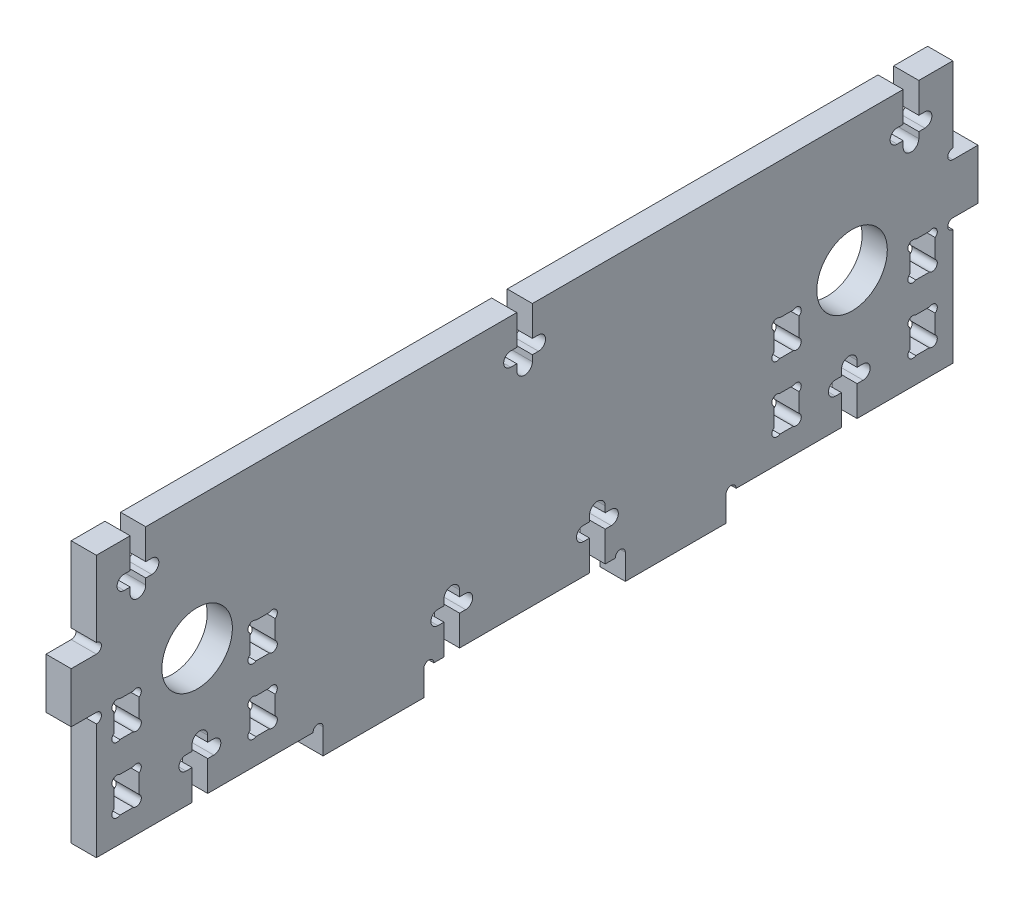
SolidWorks part; units mm, degrees
ref_plane "정면" through (0, 0, 0) normal (0, 0, 1) x (1, 0, 0)
ref_plane "윗면" through (0, 0, 0) normal (0, 1, 0) x (1, 0, 0)
ref_plane "우측면" through (0, 0, 0) normal (1, 0, 0) x (0, 0, -1)
sketch "스케치1" plane through (0, 0, 0) normal (1, 0, 0) x (0, 0, -1)
  line L1 (0, 0) -> (170, 0)
  line L2 (0, 0) -> (0, 52)
  line L3 (0, 52) -> (170, 52)
  line L4 (170, 0) -> (170, 52)
  dimension "D1" = 170
  dimension "D2" = 52
extrude "보스-돌출1" add sketch "스케치1" along normal blind 5
sketch "스케치2" plane through (5, 0, 0) normal (1, 0, 0) x (0, 0, -1)
  line L0 (170, 26) -> (150, 26) construction
  line L1 (170, 0) -> (170, 52) construction
  line L2 (150, 26) -> (20, 26) construction
  line L3 (20, 26) -> (0, 26) construction
  line L4 (0, 52) -> (0, 0) construction
  circle A0 centre (150, 26) radius 7
  circle A1 centre (20, 26) radius 7
  dimension "D2" = 14
  dimension "D1" = 20
extrude "컷-돌출1" cut sketch "스케치2" against normal blind 10
sketch "스케치3" plane through (5, 0, 0) normal (1, 0, 0) x (0, 0, -1)
  line L0 (0, 0) -> (170, 0) construction
  line L1 (45, 0) -> (65, 0)
  line L2 (45, 0) -> (45, -5)
  line L3 (45, -5) -> (65, -5)
  line L4 (65, 0) -> (65, -5)
  line L5 (0, -5) -> (45, -5) construction
  line L6 (65, -5) -> (105, -5) construction
  line L7 (125, 0) -> (105, 0)
  line L8 (125, 0) -> (125, -5)
  line L9 (125, -5) -> (105, -5)
  line L10 (105, 0) -> (105, -5)
  line L11 (125, -5) -> (170, -5) construction
  line L12 (170, -5) -> (170, 0) construction
  line L13 (0, 0) -> (0, -5) construction
  line L14 (0, 0) -> (0, -5) construction
  line L15 (0, -5) -> (45, -5) construction
  dimension "D1" = 45
  dimension "D2" = 20
extrude "보스-돌출2" add sketch "스케치3" against normal blind 5
sketch "스케치6" plane through (5, 0, 0) normal (1, 0, 0) x (0, 0, -1)
  line L0 (151, 0) -> (151, 6)
  line L1 (147.9, 10) -> (151, 10) construction
  line L2 (146.7, 6) -> (146.7, 8.8) construction
  line L3 (151, 6) -> (151, 8.8) construction
  line L4 (147.9, 0) -> (151, 0)
  line L5 (146.7, 8.8) -> (147.9, 8.8)
  line L6 (147.9, 0) -> (147.9, 6)
  line L7 (152.2, 8.8) -> (152.2, 6) construction
  line L8 (147.9, 6) -> (146.7, 6)
  line L9 (147.9, 8.8) -> (147.9, 6) construction
  line L10 (151, 8.8) -> (151, 10)
  line L11 (147.9, 6) -> (151, 6) construction
  line L12 (147.9, 8.8) -> (151, 8.8) construction
  line L13 (151, 8.8) -> (152.2, 8.8)
  line L14 (147.9, 8.8) -> (147.9, 10)
  line L15 (149.45, 10) -> (149.45, 12.1831) construction
  line L16 (152.2, 6) -> (151, 6)
  line L18 (65, 0) -> (105, 0) construction
  line L19 (101, 0) -> (101, 6)
  line L20 (97.9, 10) -> (101, 10) construction
  line L21 (96.7, 6) -> (96.7, 8.8) construction
  line L22 (101, 6) -> (101, 8.8) construction
  line L23 (97.9, 0) -> (101, 0)
  line L24 (96.7, 8.8) -> (97.9, 8.8)
  line L25 (97.9, 0) -> (97.9, 6)
  line L26 (102.2, 8.8) -> (102.2, 6) construction
  line L27 (97.9, 6) -> (96.7, 6)
  line L28 (97.9, 8.8) -> (97.9, 6) construction
  line L29 (101, 8.8) -> (101, 10)
  line L30 (97.9, 6) -> (101, 6) construction
  line L31 (97.9, 8.8) -> (101, 8.8) construction
  line L32 (101, 8.8) -> (102.2, 8.8)
  line L33 (97.9, 8.8) -> (97.9, 10)
  line L34 (99.45, 10) -> (99.45, 12.1831) construction
  line L35 (102.2, 6) -> (101, 6)
  line L37 (105, 0) -> (105, -5) construction
  line L71 (85, 52) -> (85, 0) construction
  line L72 (170, 52) -> (0, 52) construction
  line L89 (70.55, 10) -> (70.55, 12.1831) construction
  line L90 (72.1, 8.8) -> (69, 8.8) construction
  line L91 (72.1, 6) -> (69, 6) construction
  line L92 (72.1, 8.8) -> (72.1, 6) construction
  line L93 (67.8, 8.8) -> (67.8, 6) construction
  line L94 (69, 6) -> (69, 8.8) construction
  line L95 (73.3, 6) -> (73.3, 8.8) construction
  line L96 (72.1, 10) -> (69, 10) construction
  line L97 (20.55, 10) -> (20.55, 12.1831) construction
  line L98 (22.1, 8.8) -> (19, 8.8) construction
  line L99 (22.1, 6) -> (19, 6) construction
  line L100 (22.1, 8.8) -> (22.1, 6) construction
  line L101 (17.8, 8.8) -> (17.8, 6) construction
  line L102 (19, 6) -> (19, 8.8) construction
  line L103 (23.3, 6) -> (23.3, 8.8) construction
  line L104 (22.1, 10) -> (19, 10) construction
  line L123 (67.8, 6) -> (69, 6)
  line L124 (72.1, 8.8) -> (72.1, 10)
  line L125 (69, 8.8) -> (67.8, 8.8)
  line L126 (69, 8.8) -> (69, 10)
  line L127 (72.1, 6) -> (73.3, 6)
  line L128 (72.1, 0) -> (72.1, 6)
  line L129 (73.3, 8.8) -> (72.1, 8.8)
  line L130 (72.1, 0) -> (69, 0)
  line L131 (69, 0) -> (69, 6)
  line L132 (17.8, 6) -> (19, 6)
  line L133 (22.1, 8.8) -> (22.1, 10)
  line L134 (19, 8.8) -> (17.8, 8.8)
  line L135 (19, 8.8) -> (19, 10)
  line L136 (22.1, 6) -> (23.3, 6)
  line L137 (22.1, 0) -> (22.1, 6)
  line L138 (23.3, 8.8) -> (22.1, 8.8)
  line L139 (22.1, 0) -> (19, 0)
  line L140 (19, 0) -> (19, 6)
  arc A0 (151, 10) -> (147.9, 10) centre (149.45, 10) ccw
  arc A1 (146.7, 8.8) -> (146.7, 6) centre (146.7, 7.4) ccw
  arc A2 (152.2, 6) -> (152.2, 8.8) centre (152.2, 7.4) ccw
  arc A3 (101, 10) -> (97.9, 10) centre (99.45, 10) ccw
  arc A4 (96.7, 8.8) -> (96.7, 6) centre (96.7, 7.4) ccw
  arc A5 (102.2, 6) -> (102.2, 8.8) centre (102.2, 7.4) ccw
  arc A18 (67.8, 6) -> (67.8, 8.8) centre (67.8, 7.4) cw
  arc A19 (73.3, 8.8) -> (73.3, 6) centre (73.3, 7.4) cw
  arc A20 (69, 10) -> (72.1, 10) centre (70.55, 10) cw
  arc A21 (17.8, 6) -> (17.8, 8.8) centre (17.8, 7.4) cw
  arc A22 (23.3, 8.8) -> (23.3, 6) centre (23.3, 7.4) cw
  arc A23 (19, 10) -> (22.1, 10) centre (20.55, 10) cw
  dimension "D1" = 3.1
  dimension "D2" = 4
  dimension "D3" = 5.5
  dimension "D4" = 2.8
  dimension "D7" = 3.1
  dimension "D9" = 5.5
  dimension "D10" = 2.8
  dimension "D12" = 50
extrude "컷-돌출2" cut sketch "스케치6" against normal blind 10
sketch "스케치8" plane through (5, 0, 0) normal (1, 0, 0) x (0, 0, -1)
  line L0 (170, 0) -> (170, 52) construction
  line L1 (170, 35) -> (175, 35)
  line L2 (170, 35) -> (170, 25)
  line L3 (170, 25) -> (175, 25)
  line L4 (175, 35) -> (175, 25)
  line L5 (175, 52) -> (175, 35) construction
  line L8 (85, 0) -> (85, 52) construction
  line L9 (72.1, 0) -> (97.9, 0) construction
  line L10 (170, 52) -> (0, 52) construction
  line L11 (-5, 35) -> (-5, 25)
  line L12 (0, 25) -> (-5, 25)
  line L13 (0, 35) -> (0, 25)
  line L14 (0, 35) -> (-5, 35)
  line L15 (151, 0) -> (170, 0) construction
  dimension "D1" = 25
  dimension "D2" = 10
extrude "보스-돌출3" add sketch "스케치8" against normal blind 5
sketch "스케치7" plane through (5, 0, 0) normal (1, 0, 0) x (0, 0, -1)
  line L0 (65, 0) -> (69, 0) construction
  line L1 (22.1, 0) -> (45, 0) construction
  line L2 (101, 0) -> (105, 0) construction
  line L3 (125, 0) -> (147.9, 0) construction
  line L4 (170, 35) -> (170, 52) construction
  line L5 (170, 0) -> (170, 25) construction
  line L6 (0, 52) -> (0, 35) construction
  line L7 (0, 25) -> (0, 0) construction
  circle A0 centre (66, 0) radius 1
  circle A1 centre (44, 0) radius 1
  circle A2 centre (104, 0) radius 1
  circle A3 centre (126, 0) radius 1
  circle A4 centre (170, 36) radius 1
  circle A5 centre (170, 24) radius 1
  circle A6 centre (0, 36) radius 1
  circle A7 centre (0, 24) radius 1
  dimension "D1" = 2
extrude "컷-돌출3" cut sketch "스케치7" against normal blind 10
sketch "스케치10" plane through (0, 0, 0) normal (-1, 0, 0) x (0, 0, 1)
  line L0 (-166.5, 25) -> (-161.5, 18) construction
  line L1 (-166.5, 18) -> (-161.5, 18)
  line L2 (-166.5, 18) -> (-166.5, 25)
  line L3 (-166.5, 25) -> (-161.5, 25)
  line L4 (-161.5, 18) -> (-161.5, 25)
  line L5 (-161.5, 25) -> (-166.5, 18) construction
  line L6 (-85, 52) -> (-85, 0) construction
  line L7 (-139.5, 18) -> (-134.5, 18)
  line L8 (-139.5, 18) -> (-139.5, 25)
  line L9 (-139.5, 25) -> (-134.5, 25)
  line L10 (-134.5, 18) -> (-134.5, 25)
  line L11 (-166.5, 5) -> (-161.5, 5)
  line L12 (-166.5, 5) -> (-166.5, 12)
  line L13 (-166.5, 12) -> (-161.5, 12)
  line L14 (-161.5, 5) -> (-161.5, 12)
  line L15 (-139.5, 12) -> (-134.5, 12)
  line L16 (-139.5, 12) -> (-139.5, 5)
  line L17 (-139.5, 5) -> (-134.5, 5)
  line L18 (-134.5, 12) -> (-134.5, 5)
  line L19 (-170, 52) -> (0, 52) construction
  line L20 (-72.1, 0) -> (-97.9, 0) construction
  line L21 (-8.5, 25) -> (-3.5, 18) construction
  line L22 (-3.5, 25) -> (-8.5, 18) construction
  line L23 (-35.5, 12) -> (-35.5, 5)
  line L24 (-30.5, 5) -> (-35.5, 5)
  line L25 (-30.5, 12) -> (-30.5, 5)
  line L26 (-30.5, 12) -> (-35.5, 12)
  line L27 (-8.5, 5) -> (-8.5, 12)
  line L28 (-3.5, 12) -> (-8.5, 12)
  line L29 (-3.5, 5) -> (-3.5, 12)
  line L30 (-3.5, 5) -> (-8.5, 5)
  line L31 (-35.5, 18) -> (-35.5, 25)
  line L32 (-30.5, 25) -> (-35.5, 25)
  line L33 (-30.5, 18) -> (-30.5, 25)
  line L34 (-30.5, 18) -> (-35.5, 18)
  line L35 (-8.5, 18) -> (-8.5, 25)
  line L36 (-3.5, 25) -> (-8.5, 25)
  line L37 (-3.5, 18) -> (-3.5, 25)
  line L38 (-3.5, 18) -> (-8.5, 18)
extrude "컷-돌출4" cut sketch "스케치10" against normal blind 10
sketch "스케치11" plane through (5, 0, 0) normal (1, 0, 0) x (0, 0, -1)
  line L0 (85, 52) -> (85, 0) construction
  line L1 (170, 52) -> (0, 52) construction
  line L2 (72.1, 0) -> (97.9, 0) construction
  line L3 (161.5, 25) -> (166.5, 18) construction
  line L4 (166.5, 25) -> (161.5, 18) construction
  line L5 (139.5, 18) -> (161.5, 18) construction
  line L6 (161.5, 18) -> (161.5, 12) construction
  line L7 (161.5, 12) -> (139.5, 12) construction
  line L8 (139.5, 12) -> (139.5, 18) construction
  line L9 (150.5, 18) -> (150.5, 12) construction
  line L10 (139.5, 15) -> (161.5, 15) construction
  line L11 (134.5, 25) -> (139.5, 18) construction
  line L12 (139.5, 25) -> (134.5, 18) construction
  line L13 (139.5, 5) -> (134.5, 12) construction
  line L14 (134.5, 5) -> (139.5, 12) construction
  line L15 (166.5, 5) -> (161.5, 12) construction
  line L16 (161.5, 5) -> (166.5, 12) construction
  line L17 (8.5, 5) -> (3.5, 12) construction
  line L18 (3.5, 5) -> (8.5, 12) construction
  line L19 (35.5, 5) -> (30.5, 12) construction
  line L20 (30.5, 5) -> (35.5, 12) construction
  line L21 (30.5, 25) -> (35.5, 18) construction
  line L22 (35.5, 25) -> (30.5, 18) construction
  line L23 (30.5, 15) -> (8.5, 15) construction
  line L24 (19.5, 18) -> (19.5, 12) construction
  line L25 (30.5, 12) -> (30.5, 18) construction
  line L26 (8.5, 12) -> (30.5, 12) construction
  line L27 (8.5, 18) -> (8.5, 12) construction
  line L28 (30.5, 18) -> (8.5, 18) construction
  line L29 (3.5, 25) -> (8.5, 18) construction
  line L30 (8.5, 25) -> (3.5, 18) construction
  circle A0 centre (165.9188, 24.1863) radius 1
  circle A1 centre (162.0812, 24.1863) radius 1
  circle A2 centre (165.9188, 18.8137) radius 1
  circle A3 centre (162.0812, 18.8137) radius 1
  circle A4 centre (138.9188, 18.8137) radius 1
  circle A5 centre (135.0812, 18.8137) radius 1
  circle A6 centre (138.9188, 24.1863) radius 1
  circle A7 centre (135.0812, 24.1863) radius 1
  circle A8 centre (135.0812, 5.8137) radius 1
  circle A9 centre (138.9188, 5.8137) radius 1
  circle A10 centre (135.0812, 11.1863) radius 1
  circle A11 centre (138.9188, 11.1863) radius 1
  circle A12 centre (162.0812, 11.1863) radius 1
  circle A13 centre (165.9188, 11.1863) radius 1
  circle A14 centre (162.0812, 5.8137) radius 1
  circle A15 centre (165.9188, 5.8137) radius 1
  circle A16 centre (4.0812, 5.8137) radius 1
  circle A17 centre (7.9188, 5.8137) radius 1
  circle A18 centre (4.0812, 11.1863) radius 1
  circle A19 centre (7.9188, 11.1863) radius 1
  circle A20 centre (31.0812, 11.1863) radius 1
  circle A21 centre (34.9188, 11.1863) radius 1
  circle A22 centre (31.0812, 5.8137) radius 1
  circle A23 centre (34.9188, 5.8137) radius 1
  circle A24 centre (34.9188, 24.1863) radius 1
  circle A25 centre (31.0812, 24.1863) radius 1
  circle A26 centre (34.9188, 18.8137) radius 1
  circle A27 centre (31.0812, 18.8137) radius 1
  circle A28 centre (7.9188, 18.8137) radius 1
  circle A29 centre (4.0812, 18.8137) radius 1
  circle A30 centre (7.9188, 24.1863) radius 1
  circle A31 centre (4.0812, 24.1863) radius 1
  dimension "D1" = 2
extrude "컷-돌출5" cut sketch "스케치11" against normal blind 10
sketch "스케치12" plane through (5, 0, 0) normal (1, 0, 0) x (0, 0, -1)
  line L0 (160.15, 52) -> (160.15, 46)
  line L1 (163.25, 42) -> (160.15, 42) construction
  line L2 (164.45, 46) -> (164.45, 43.2) construction
  line L3 (160.15, 46) -> (160.15, 43.2) construction
  line L4 (163.25, 52) -> (160.15, 52)
  line L5 (164.45, 43.2) -> (163.25, 43.2)
  line L6 (163.25, 52) -> (163.25, 46)
  line L7 (158.95, 43.2) -> (158.95, 46) construction
  line L8 (163.25, 46) -> (164.45, 46)
  line L9 (163.25, 43.2) -> (163.25, 46) construction
  line L10 (160.15, 43.2) -> (160.15, 42)
  line L11 (163.25, 46) -> (160.15, 46) construction
  line L12 (163.25, 43.2) -> (160.15, 43.2) construction
  line L13 (160.15, 43.2) -> (158.95, 43.2)
  line L14 (163.25, 43.2) -> (163.25, 42)
  line L15 (161.7, 42) -> (161.7, 40.45) construction
  line L16 (158.95, 46) -> (160.15, 46)
  line L17 (164.45, 44.6) -> (163.25, 44.6) construction
  line L18 (158.95, 44.6) -> (160.15, 44.6) construction
  line L19 (161.7, 43.2) -> (161.7, 42) construction
  line L20 (158.95, 44.6) -> (157.55, 44.6) construction
  line L21 (164.45, 44.6) -> (165.85, 44.6) construction
  line L22 (170, 52) -> (0, 52) construction
  line L23 (82.25, 46) -> (83.45, 46)
  line L24 (86.55, 46) -> (83.45, 46) construction
  line L25 (83.45, 52) -> (83.45, 46)
  line L26 (153.5, 52) -> (153.5, 55) construction
  line L27 (86.55, 42) -> (83.45, 42) construction
  line L28 (86.55, 52) -> (86.55, 46)
  line L29 (87.75, 44.6) -> (89.15, 44.6) construction
  line L30 (87.75, 43.2) -> (86.55, 43.2)
  line L31 (85, 43.2) -> (85, 42) construction
  line L32 (82.25, 44.6) -> (80.85, 44.6) construction
  line L33 (82.25, 43.2) -> (82.25, 46) construction
  line L34 (86.55, 52) -> (83.45, 52)
  line L35 (86.55, 46) -> (87.75, 46)
  line L36 (83.45, 43.2) -> (82.25, 43.2)
  line L37 (86.55, 43.2) -> (86.55, 42)
  line L38 (83.45, 46) -> (83.45, 43.2) construction
  line L39 (86.55, 43.2) -> (83.45, 43.2) construction
  line L40 (82.25, 44.6) -> (83.45, 44.6) construction
  line L41 (85, 42) -> (85, 40.45) construction
  line L42 (87.75, 44.6) -> (86.55, 44.6) construction
  line L43 (83.45, 43.2) -> (83.45, 42)
  line L44 (87.75, 46) -> (87.75, 43.2) construction
  line L45 (86.55, 43.2) -> (86.55, 46) construction
  line L47 (16.5, 52) -> (0, 52) construction
  line L48 (16.5, 52) -> (16.5, 55) construction
  line L49 (8.25, 52) -> (8.25, 44) construction
  line L50 (11, 46) -> (11, 43.2) construction
  line L51 (5.5, 43.2) -> (5.5, 46) construction
  line L52 (11, 44.6) -> (12.4, 44.6) construction
  line L53 (6.7, 43.2) -> (6.7, 42)
  line L54 (9.8, 43.2) -> (9.8, 46) construction
  line L55 (9.8, 43.2) -> (6.7, 43.2) construction
  line L56 (9.8, 43.2) -> (9.8, 42)
  line L57 (11, 44.6) -> (9.8, 44.6) construction
  line L58 (9.8, 46) -> (11, 46)
  line L59 (11, 43.2) -> (9.8, 43.2)
  line L60 (6.7, 43.2) -> (5.5, 43.2)
  line L61 (5.5, 46) -> (6.7, 46)
  line L62 (9.8, 52) -> (6.7, 52)
  line L63 (5.5, 44.6) -> (4.1, 44.6) construction
  line L64 (9.8, 46) -> (6.7, 46) construction
  line L65 (9.8, 42) -> (6.7, 42) construction
  line L66 (8.25, 43.2) -> (8.25, 42) construction
  line L67 (9.8, 52) -> (9.8, 46)
  line L68 (5.5, 44.6) -> (6.7, 44.6) construction
  line L69 (6.7, 52) -> (6.7, 46)
  line L70 (6.7, 46) -> (6.7, 43.2) construction
  line L71 (8.25, 42) -> (8.25, 40.45) construction
  arc A0 (160.15, 42) -> (163.25, 42) centre (161.7, 42) ccw
  arc A1 (164.45, 43.2) -> (164.45, 46) centre (164.45, 44.6) ccw
  arc A2 (158.95, 46) -> (158.95, 43.2) centre (158.95, 44.6) ccw
  arc A3 (87.75, 43.2) -> (87.75, 46) centre (87.75, 44.6) ccw
  arc A4 (82.25, 46) -> (82.25, 43.2) centre (82.25, 44.6) ccw
  arc A5 (83.45, 42) -> (86.55, 42) centre (85, 42) ccw
  arc A6 (5.5, 46) -> (5.5, 43.2) centre (5.5, 44.6) ccw
  arc A7 (6.7, 42) -> (9.8, 42) centre (8.25, 42) ccw
  arc A8 (11, 43.2) -> (11, 46) centre (11, 44.6) ccw
  point P25 (85, 52)
  dimension "D1" = 3.1
  dimension "D2" = 5.5
  dimension "D3" = 2.8
  dimension "D4" = 1.2
  dimension "D5" = 6
  dimension "D6" = 3.1
  dimension "D7" = 6.65
  dimension "D8" = 3.1
  dimension "D9" = 5.5
  dimension "D10" = 2.8
  dimension "D11" = 1.2
  dimension "D12" = 6
  dimension "D13" = 3.1
  dimension "D14" = 5.5
  dimension "D15" = 2.8
  dimension "D16" = 1.2
  dimension "D17" = 6
  dimension "D18" = 3.1
extrude "컷-돌출6" cut sketch "스케치12" against normal blind 10
